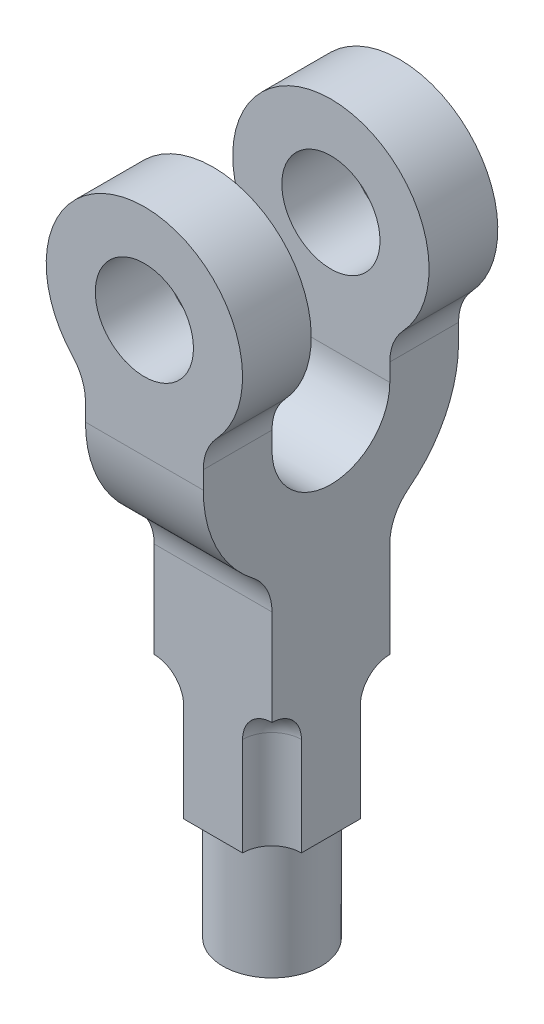
SolidWorks part; units mm, degrees
ref_plane "Front Plane" through (0, 0, 0) normal (1, 0, 0) x (0, 1, 0)
ref_plane "Top Plane" through (0, 0, 0) normal (0, 0, 1) x (0, 1, 0)
ref_plane "Right Plane" through (0, 0, 0) normal (0, 1, 0) x (-1, 0, 0)
sketch "Sketch1" plane through (0, 0, 0) normal (1, 0, 0) x (0, 1, 0)
  line L0 (37, 26) -> (81, 26)
  line L1 (37, -12) -> (-37, -12)
  line L2 (37, -12) -> (37, 12)
  line L3 (37, 12) -> (-37, 12)
  line L4 (-37, -12) -> (-37, 12)
  line L5 (37, -12) -> (-37, 12) construction
  line L6 (37, 12) -> (-37, -12) construction
  line L7 (37, 12) -> (81, 12)
  line L8 (37, -12) -> (81, -12)
  line L9 (37, -26) -> (81, -26)
  line L10 (81, -26) -> (81, -12)
  line L11 (81, 26) -> (81, 12)
  line L12 (37, 26) -> (37, 12)
  line L13 (37, -12) -> (37, -26)
  circle A0 centre (37, 0) radius 12
  circle A1 centre (37, 0) radius 26
  point P0 (0, 0)
  dimension "D3" = 24
  dimension "D1" = 24
  dimension "D2" = 74
  dimension "D5" = 118
  dimension "D4" = 14
extrude "Boss-Extrude1" add sketch "Sketch1" along normal blind 24 contours L12 A1 L3 | A1 L3 L4 L1 | L1 A1 L13 | L3 A1 L1 A0 | L13 L9 L10 L8 | L7 L11 L0 L12 region at (0, 27.9255, 17.7534) region at (0, 19.9707, 0) region at (0, -12.5148, 0) region at (0, 27.9255, -17.7534)
sketch "Sketch2" plane through (0, -37, 0) normal (0, -1, 0) x (1, 0, 0)
  line L0 (24, 12) -> (0, 12) construction
  line L2 (24, -12) -> (24, 12) construction
  circle A0 centre (12, 0) radius 10
  point P5 (10, 0)
  point P7 (-9.53, -3.2018)
  dimension "D1" = 20
  dimension "D2" = 12
  dimension "D3" = 12
extrude "Boss-Extrude2" add sketch "Sketch2" along normal blind 24
sketch "Sketch3" plane through (24, 0, 0) normal (1, 0, 0) x (0, 1, 0)
  line L2 (-37, 12) -> (-37, 6)
  line L3 (-37, 6) -> (-17, 6)
  line L6 (-11, 12) -> (-37, 12)
  arc A0 (-17, 6) -> (-11, 12) centre (-17, 12) ccw
  dimension "D2" = 6
  dimension "D1" = 20
revolve "Cut-Revolve2" cut sketch "Sketch3" angle 360 about axis through (24, 0, 12) along (0, -1, 0)
pattern_circular "CirPattern1" count 4 every 90 about axis through (12, -61, 0) along (0, -1, 0) of "Cut-Revolve2"
sketch "Sketch4" plane through (0, 0, 26) normal (0, 0, 1) x (1, 0, 0)
  line L0 (0, -37) -> (0, 61) construction
  line L1 (0, 61) -> (12, 61)
  line L2 (24, 37) -> (24, 81) construction
  line L3 (0, 81) -> (24, 81)
  line L4 (0, 81) -> (0, 61)
  line L5 (0, 61) -> (24, 61)
  line L6 (24, 81) -> (24, 61)
  circle A0 centre (12, 61) radius 20
  circle A1 centre (12, 61) radius 10
  line M9 (0, 81) -> (0, 37)
  line M11 (24, 37) -> (24, 81)
  line M12 (24, 81) -> (0, 81)
  dimension "D3" = 20
  dimension "D4" = 40
  dimension "D1" = 98
  dimension "D2" = 12
extrude "Boss-Extrude4" add sketch "Sketch4" against normal through all from offset 38 contours A0 M11 | L4 A0 M9 region at (-3.2621, 61, 26) region at (27.2621, 61, 26) offset against normal yes
extrude "Boss-Extrude5" add sketch "Sketch4<3>" against normal up to surface (14 mm away) contours A0 M11 | L4 A0 M9 region at (-3.2621, 61, 26) region at (27.2621, 61, 26) up to face at (12, 59, 12)
sketch "Sketch4<3>" plane through (0, 0, 26) normal (0, 0, 1) x (1, 0, 0) same geometry as "Sketch4"
extrude "Cut-Extrude1" cut sketch "Sketch4<4>" against normal through all contours A0 L6 M12 | A0 L3 M9 | L5 A1 | L5 A1 region at (12, 65.2441, 26) region at (12, 56.7559, 26) region at (2.9367, 79.8238, 26) region at (21.0633, 79.8238, 26)
sketch "Sketch4<4>" plane through (0, 0, 26) normal (0, 0, 1) x (1, 0, 0) same geometry as "Sketch4"
fillet "Fillet1" radius 10 4 edges at (0, 45, 19) (0, 45, -19) (24, 45, 19) (24, 45, -19)
fillet "Fillet2" radius 10 2 edges at (12, 13.9349, -12) (12, 13.9349, 12)
